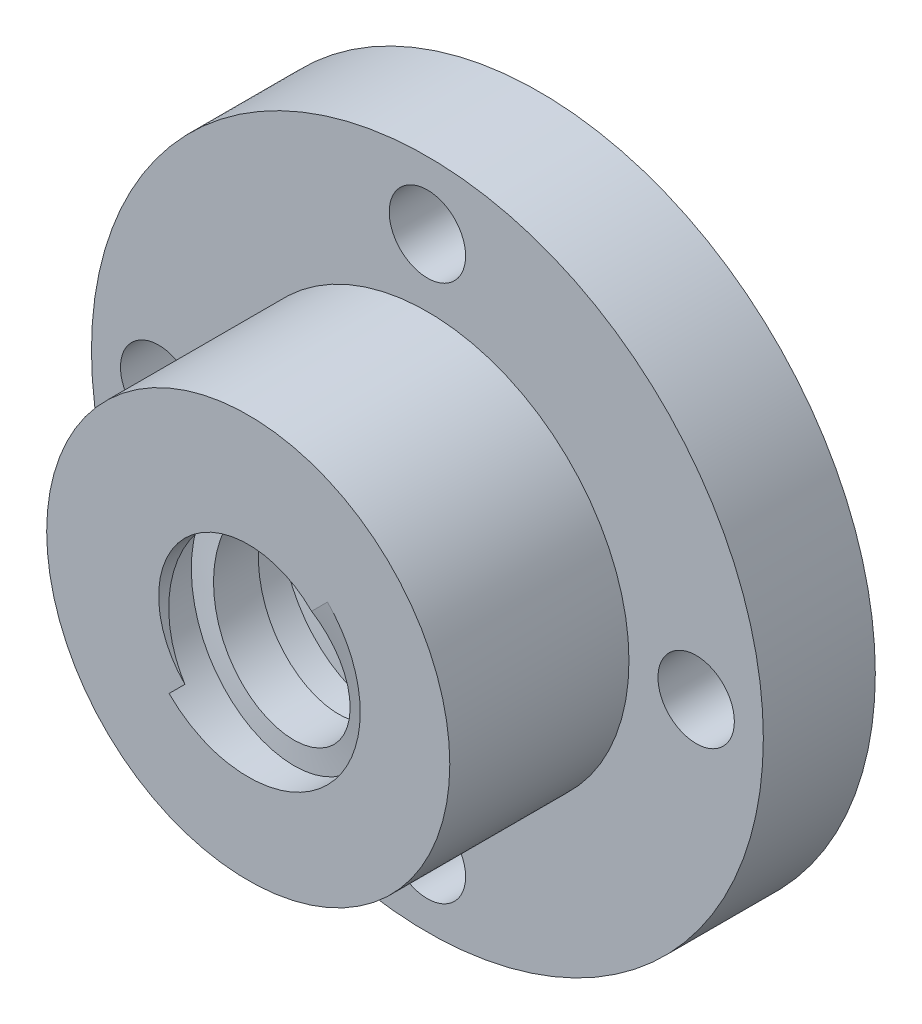
SolidWorks part; units mm, degrees
material "Brass"
ref_plane "Front Plane" through (0, 0, 0) normal (0, 0, 1) x (1, 0, 0)
ref_plane "Top Plane" through (0, 0, 0) normal (0, 1, 0) x (1, 0, 0)
ref_plane "Right Plane" through (0, 0, 0) normal (1, 0, 0) x (0, 0, -1)
sketch "Sketch1" plane through (0, 0, 0) normal (0, 0, 1) x (1, 0, 0)
  circle A0 centre (0, 0) radius 4
  circle A1 centre (0, 0) radius 15
  dimension "D1" = 8
  dimension "D2" = 30
extrude "Boss-Extrude1" add sketch "Sketch1" along normal blind 5
sketch "Sketch2" plane through (0, 0, 5) normal (0, 0, 1) x (1, 0, 0)
  circle A0 centre (0, 0) radius 4 construction
  circle A1 centre (0, 0) radius 4
  circle A2 centre (0, 0) radius 9
  dimension "D1" = 5
extrude "Boss-Extrude2" add sketch "Sketch2" along normal blind 8
ref_plane "Plane1" through (0, 0, -10) normal (0, 0, -1) x (-1, 0, 0)
sketch "Sketch3" plane through (0, 0, -10) normal (0, 0, -1) x (-1, 0, 0)
  circle A0 centre (0, 0) radius 4 construction
  circle A1 centre (0, 0) radius 4
curve "Helix/Spiral1" pitch 4 height 40 radius 4 centre (0, 0, -10) axis (0, 0, 1) start towards (0.7071, 0.7071, 0)
sketch "Sketch4" plane through (0, 0, 0) normal (0, 1, 0) x (1, 0, 0)
  line L1 (3, -4.5) -> (5, -4.5)
  line L2 (3, -4.5) -> (3, -6.5)
  line L3 (3, -6.5) -> (5, -6.5)
  line L4 (5, -4.5) -> (5, -6.5)
  line L5 (3, -4.5) -> (5, -6.5) construction
  line L6 (3, -6.5) -> (5, -4.5) construction
  point P0 (4, -5.5)
  dimension "D1" = 2
sweep "Cut-Sweep1" cut profiles "Sketch4" path "Helix/Spiral1"
sketch "Sketch5" plane through (0, 0, 5) normal (0, 0, 1) x (1, 0, 0)
  line L0 (0, 0) -> (0, 12) construction
  circle A0 centre (0, 12) radius 1.7051
  circle A1 centre (12, 0) radius 1.7051
  circle A2 centre (0, -12) radius 1.7051
  circle A3 centre (-12, 0) radius 1.7051
  dimension "D1" = 3.4103
  dimension "D2" = 12
  dimension "D4" = 12
  dimension "D3" = 4
extrude "Cut-Extrude1" cut sketch "Sketch5" against normal blind 8
